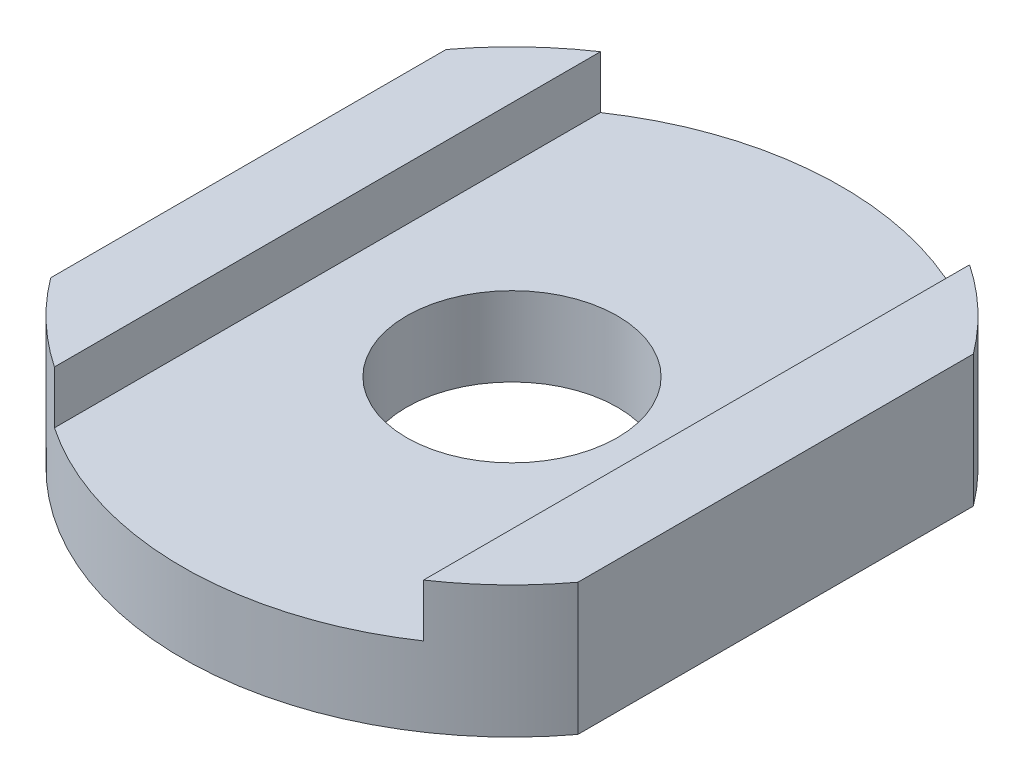
SolidWorks part; units mm, degrees
ref_plane "Front Plane" through (0, 0, 0) normal (0, 0, 1) x (1, 0, 0)
ref_plane "Top Plane" through (0, 0, 0) normal (0, 1, 0) x (1, 0, 0)
ref_plane "Right Plane" through (0, 0, 0) normal (1, 0, 0) x (0, 0, -1)
sketch "Sketch1" plane through (0, 0, 0) normal (0, 1, 0) x (1, 0, 0)
  line L0 (0, -16.4208) -> (0, 16.4208) construction
  line L1 (-10, -7.5) -> (-10, 7.5)
  line L2 (-7, 10.3562) -> (-7, -10.3562)
  line L3 (7, 10.3562) -> (7, -10.3562)
  line L4 (10, -7.5) -> (10, 7.5)
  circle A0 centre (0, 0) radius 4
  arc A1 (-10, -7.5) -> (10, -7.5) centre (0, 0) ccw
  arc A2 (10, 7.5) -> (-10, 7.5) centre (0, 0) ccw
  point P7 (0, 0)
  dimension "D1" = 8
  dimension "D2" = 3
  dimension "D4" = 25
  dimension "D3" = 20
extrude "Boss-Extrude1" add sketch "Sketch1" along normal blind 3 contours L2 A2 L1 A1 | A1 L0 A0 A2 L2 | L0 A1 L3 A2 A0 | L4 A2 L3 A1 region at (-3.5844, 0, 11.7038) region at (0.2596, 0, 8.25) region at (-8.4223, 0, 0) region at (8.4223, 0, 0)
extrude "Boss-Extrude2" add sketch "Sketch1<3>" along normal blind 5 contours L2 A2 L1 A1 | L4 A2 L3 A1 region at (-8.4223, 0, 0) region at (8.4223, 0, 0)
sketch "Sketch1<3>" plane through (0, 0, 0) normal (0, 1, 0) x (1, 0, 0) same geometry as "Sketch1"
